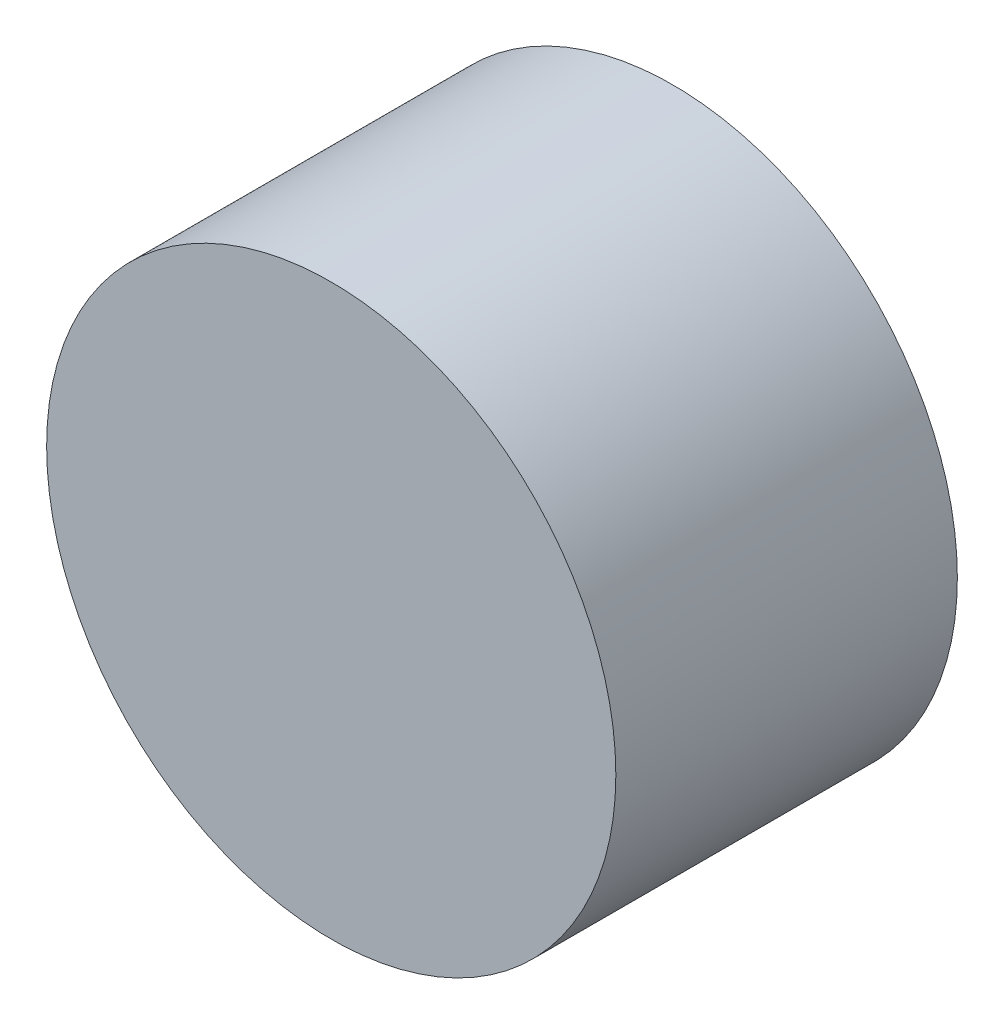
SolidWorks part; units mm, degrees
ref_plane "Front Plane" through (0, 0, 0) normal (0, 0, 1) x (1, 0, 0)
ref_plane "Top Plane" through (0, 0, 0) normal (0, 1, 0) x (1, 0, 0)
ref_plane "Right Plane" through (0, 0, 0) normal (1, 0, 0) x (0, 0, -1)
sketch "Sketch1" plane through (0, 0, 0) normal (0, 0, 1) x (1, 0, 0)
  circle A0 centre (0, 0) radius 22.5
  dimension "D1" = 45
extrude "Boss-Extrude1" add sketch "Sketch1" along normal mid plane 27
ref_plane "Plane1" through (0, 0, 0) normal (0, 0, -1) x (-1, 0, 0)
